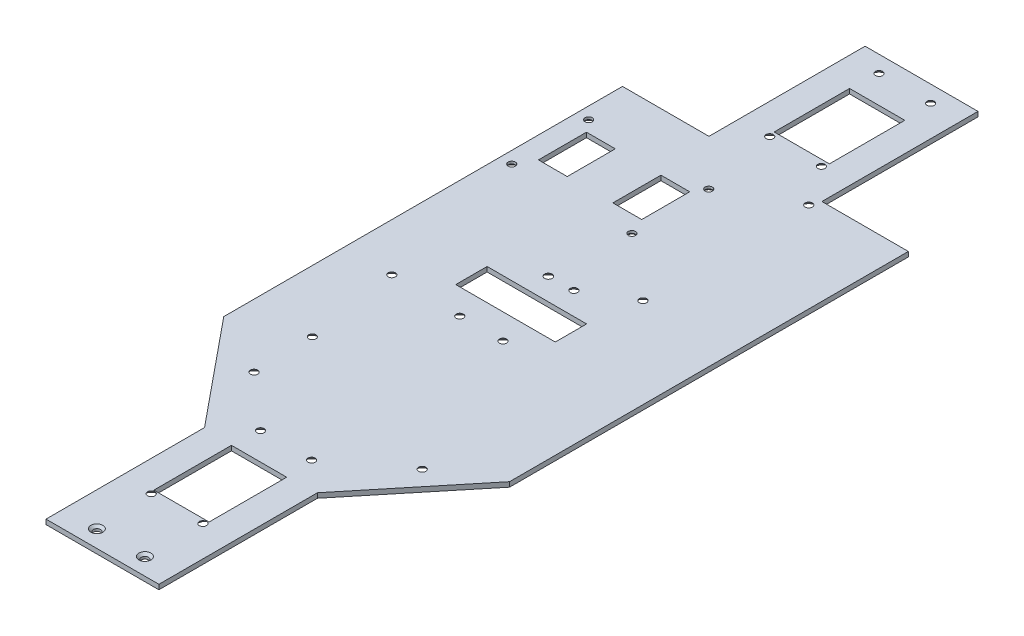
SolidWorks part; units mm, degrees
material "Cast Alloy Steel"
ref_plane "Front Plane" through (0, 0, 0) normal (0, 0, 1) x (1, 0, 0)
ref_plane "Top Plane" through (0, 0, 0) normal (0, 1, 0) x (1, 0, 0)
ref_plane "Right Plane" through (0, 0, 0) normal (1, 0, 0) x (0, 0, -1)
sketch "Sketch2" plane through (0, 0, 0) normal (0, 1, 0) x (1, 0, 0)
  line L0 (0, 0) -> (47, 0)
  line L1 (47, 0) -> (47, 66)
  line L2 (0, 0) -> (0, 66)
  line L3 (47, 66) -> (83, 110)
  line L4 (0, 66) -> (-36, 110)
  line L5 (-36, 110) -> (-36, 276)
  line L6 (83, 110) -> (83, 276)
  line L7 (-36, 276) -> (0, 276)
  line L8 (0, 276) -> (0, 341)
  line L9 (0, 341) -> (47, 341)
  line L10 (47, 341) -> (47, 276)
  line L11 (47, 276) -> (83, 276)
sketch "Sketch4" plane through (0, 0, 0) normal (0, 1, 0) x (1, 0, 0)
  line L0 (0, 341) -> (0, 276)
  line L1 (0, 276) -> (-36, 276)
  line L2 (-36, 276) -> (-36, 110)
  line L3 (-36, 110) -> (0, 66)
  line L4 (0, 66) -> (0, 0)
  line L5 (0, 0) -> (47, 0)
  line L6 (47, 0) -> (47, 66)
  line L7 (47, 66) -> (83, 110)
  line L8 (83, 110) -> (83, 276)
  line L9 (83, 276) -> (47, 276)
  line L10 (47, 276) -> (47, 341)
  line L11 (47, 341) -> (0, 341)
extrude "Boss-Extrude2" add sketch "Sketch4" along normal blind 2
sketch "Sketch5" plane through (0, 2, 0) normal (0, 1, 0) x (1, 0, 0)
  line L0 (0, 0) -> (47, 0) construction
  line L1 (12, 29) -> (35, 29)
  line L2 (12, 29) -> (12, 55)
  line L3 (12, 55) -> (35, 55)
  line L4 (35, 29) -> (35, 55)
  line L5 (0, 66) -> (0, 0) construction
  line L6 (47, 0) -> (47, 66) construction
  dimension "D1" = 29
  dimension "D2" = 12
  dimension "D3" = 26
  dimension "D4" = 12
extrude "Cut-Extrude1" cut sketch "Sketch5" against normal blind 2
sketch "Sketch6" plane through (0, 2, 0) normal (0, 1, 0) x (1, 0, 0)
  line L0 (47, 341) -> (0, 341) construction
  line L1 (12, 312) -> (35, 312)
  line L2 (12, 312) -> (12, 286)
  line L3 (12, 286) -> (35, 286)
  line L4 (35, 312) -> (35, 286)
  line L5 (47, 276) -> (47, 341) construction
  line L6 (0, 341) -> (0, 276) construction
  dimension "D1" = 29
  dimension "D2" = 12
  dimension "D3" = 12
  dimension "D4" = 26
extrude "Cut-Extrude2" cut sketch "Sketch6" against normal blind 2
sketch "Sketch7" plane through (0, 2, 0) normal (0, 1, 0) x (1, 0, 0)
  line L0 (0, 276) -> (-36, 276) construction
  line L1 (-27, 252) -> (-15, 252)
  line L2 (-27, 252) -> (-27, 232)
  line L3 (-27, 232) -> (-15, 232)
  line L4 (-15, 252) -> (-15, 232)
  line L5 (-36, 276) -> (-36, 110) construction
  dimension "D1" = 24
  dimension "D2" = 20
  dimension "D3" = 9
  dimension "D4" = 12
extrude "Cut-Extrude3" cut sketch "Sketch7" against normal blind 2
sketch "Sketch8" plane through (0, 2, 0) normal (0, 1, 0) x (1, 0, 0)
  line L0 (-15, 232) -> (-15, 252) construction
  line L1 (4, 252) -> (16, 252)
  line L2 (4, 252) -> (4, 232)
  line L3 (4, 232) -> (16, 232)
  line L4 (16, 252) -> (16, 232)
  line L5 (-15, 252) -> (-27, 252) construction
  dimension "D1" = 19
  dimension "D2" = 12
  dimension "D3" = 20
  dimension "D4" = 0
extrude "Cut-Extrude4" cut sketch "Sketch8" against normal blind 2
sketch "Sketch9" plane through (0, 2, 0) normal (0, 1, 0) x (1, 0, 0)
  circle A0 centre (-9.6681, 96.2994) radius 1.5
  circle A1 centre (60.3319, 96.2994) radius 1.5
  dimension "D1" = 3
  dimension "D2" = 3
extrude "Cut-Extrude5" cut sketch "Sketch9" against normal blind 4
sketch "Sketch10" plane through (0, 2, 0) normal (0, 1, 0) x (1, 0, 0)
  circle A0 centre (45.5156, 272) radius 1.5
  circle A1 centre (45.5156, 203) radius 1.5
extrude "Cut-Extrude6" cut sketch "Sketch10" against normal blind 4
sketch "Sketch11" plane through (0, 2, 0) normal (0, 1, 0) x (1, 0, 0)
  circle A0 centre (27.4536, 192.2994) radius 1.5
  circle A1 centre (16.9994, 192.1176) radius 1.5565
  circle A2 centre (12.9536, 159.2994) radius 1.5
  circle A3 centre (30.9536, 159.2994) radius 1.5
extrude "Cut-Extrude7" cut sketch "Sketch11" against normal blind 4
chamfer "Chamfer1" distance 2 angle 45 8 edges at (45.5156, 0, -270.5) (45.5156, 0, -201.5) (27.4536, 0, -190.7994) (16.9994, 0, -190.5611) (12.9536, 0, -157.7994) (30.9536, 0, -157.7994) (60.3319, 0, -94.7994) (-9.6681, 0, -94.7994)
sketch "Sketch12" plane through (0, 2, 0) normal (0, 1, 0) x (1, 0, 0)
  line L1 (42.1678, 169.8498) -> (0.7406, 169.8498)
  line L2 (42.1678, 169.8498) -> (42.1678, 182.8979)
  line L3 (42.1678, 182.8979) -> (0.7406, 182.8979)
  line L4 (0.7406, 169.8498) -> (0.7406, 182.8979)
  line L5 (42.1678, 169.8498) -> (0.7406, 182.8979) construction
  line L6 (42.1678, 182.8979) -> (0.7406, 169.8498) construction
  point P0 (21.4542, 176.3738)
extrude "Cut-Extrude8" cut sketch "Sketch12" against normal blind 4
sketch "Sketch13" plane through (0, 2, 0) normal (0, 1, 0) x (1, 0, 0)
  circle A0 centre (-16.0855, 160.0418) radius 1.5
  circle A1 centre (-10.2825, 121.1647) radius 1.5
  dimension "D1" = 3
extrude "Cut-Extrude9" cut sketch "Sketch13" against normal blind 10
chamfer "Chamfer2" distance 2 angle 45 2 edges at (-16.0855, 0, -158.5418) (-10.2825, 0, -119.6647)
sketch "Sketch14" plane through (0, 0, 0) normal (0, -1, 0) x (-1, 0, 0)
  line L0 (-12, 55) -> (-12, 29) construction
  line L1 (-35, 29) -> (-12, 29)
  line L2 (-35, 29) -> (-35, 32.8963)
  line L3 (-35, 32.8963) -> (-12, 32.8963)
  line L4 (-12, 29) -> (-12, 32.8963)
extrude "Boss-Extrude3" add sketch "Sketch14" against normal blind 2
sketch "Sketch15" plane through (0, 0, 0) normal (0, -1, 0) x (1, 0, 0)
  line L1 (35, -55) -> (12, -55)
  line L2 (35, -55) -> (35, -61.0161)
  line L3 (35, -61.0161) -> (12, -61.0161)
  line L4 (12, -55) -> (12, -61.0161)
extrude "Cut-Extrude10" cut sketch "Sketch15" against normal blind 2
sketch "Sketch16" plane through (0, 0, 0) normal (0, -1, 0) x (1, 0, 0)
  line L1 (35, -61.0161) -> (12, -61.0161)
  line L2 (35, -61.0161) -> (35, -65.206)
  line L3 (35, -65.206) -> (12, -65.206)
  line L4 (12, -61.0161) -> (12, -65.206)
  dimension "D1" = 23
extrude "Cut-Extrude11" cut sketch "Sketch16" against normal blind 2
sketch "Sketch17" plane through (0, 2, 0) normal (0, 1, 0) x (1, 0, 0)
  circle A0 centre (34.0107, 76.5494) radius 1.5
  circle A1 centre (12.7607, 76.5494) radius 1.5
  circle A2 centre (12.7607, 31.0494) radius 1.5
  circle A3 centre (34.2607, 31.0494) radius 1.5
extrude "Cut-Extrude12" cut sketch "Sketch17" against normal blind 2
chamfer "Chamfer4" distance 2 angle 45 4 edges at (34.2607, 0, -29.5494) (12.7607, 0, -29.5494) (34.0107, 0, -75.0494) (12.7607, 0, -75.0494)
sketch "Sketch19" plane through (0, 0, 0) normal (0, -1, 0) x (1, 0, 0)
  line L1 (12, -312) -> (35, -312)
  line L2 (12, -312) -> (12, -319.9222)
  line L3 (12, -319.9222) -> (35, -319.9222)
  line L4 (35, -312) -> (35, -319.9222)
  dimension "D1" = 23
extrude "Cut-Extrude13" cut sketch "Sketch19" against normal blind 2
sketch "Sketch20" plane through (0, 0, 0) normal (0, -1, 0) x (1, 0, 0)
  line L1 (35, -319.9222) -> (12, -319.9222)
  line L2 (35, -319.9222) -> (35, -322.5336)
  line L3 (35, -322.5336) -> (12, -322.5336)
  line L4 (12, -319.9222) -> (12, -322.5336)
  dimension "D1" = 23
extrude "Cut-Extrude14" cut sketch "Sketch20" against normal blind 2
sketch "Sketch22" plane through (0, 0, 0) normal (0, -1, 0) x (-1, 0, 0)
  line L0 (-12, 322.5336) -> (-12, 286) construction
  line L1 (-35, 286) -> (-12, 286)
  line L2 (-35, 286) -> (-35, 291.1376)
  line L3 (-35, 291.1376) -> (-12, 291.1376)
  line L4 (-12, 286) -> (-12, 291.1376)
extrude "Boss-Extrude5" add sketch "Sketch22" against normal blind 2
sketch "Sketch23" plane through (0, 2, 0) normal (0, 1, 0) x (1, 0, 0)
  circle A0 centre (12.7412, 334.0491) radius 1.5
  circle A1 centre (34.2412, 334.0491) radius 1.5
  circle A2 centre (34.2412, 288.5491) radius 1.5
  circle A3 centre (12.7412, 288.5491) radius 1.5
extrude "Cut-Extrude16" cut sketch "Sketch23" against normal blind 2
chamfer "Chamfer6" distance 2 angle 45 4 edges at (34.2412, 0, -287.0491) (12.7412, 0, -287.0491) (12.7412, 0, -332.5491) (34.2412, 0, -332.5491)
sketch "Sketch24" plane through (0, 2, 0) normal (0, 1, 0) x (1, 0, 0)
  circle A0 centre (-31.0315, 256.9284) radius 1.5
  circle A1 centre (-31.0315, 224.9284) radius 1.5
  circle A2 centre (18.9685, 256.9284) radius 1.5
  circle A3 centre (18.9685, 224.9284) radius 1.5
extrude "Cut-Extrude17" cut sketch "Sketch24" against normal blind 10
chamfer "Chamfer7" distance 1 angle 45 4 edges at (18.9685, 0, -255.4284) (18.9685, 0, -223.4284) (-31.0315, 0, -255.4284) (-31.0315, 0, -223.4284)
sketch "Sketch25" plane through (0, 0, 0) normal (0, -1, 0) x (1, 0, 0)
  circle A0 centre (14.0873, -7.0925) radius 1.5
  circle A1 centre (34.0873, -7.0925) radius 1.5
  dimension "D1" = 3
extrude "Cut-Extrude18" cut sketch "Sketch25" against normal up to next
chamfer "Chamfer8" distance 1 angle 45 2 edges at (34.0873, 2, -5.5925) (14.0873, 2, -5.5925)
